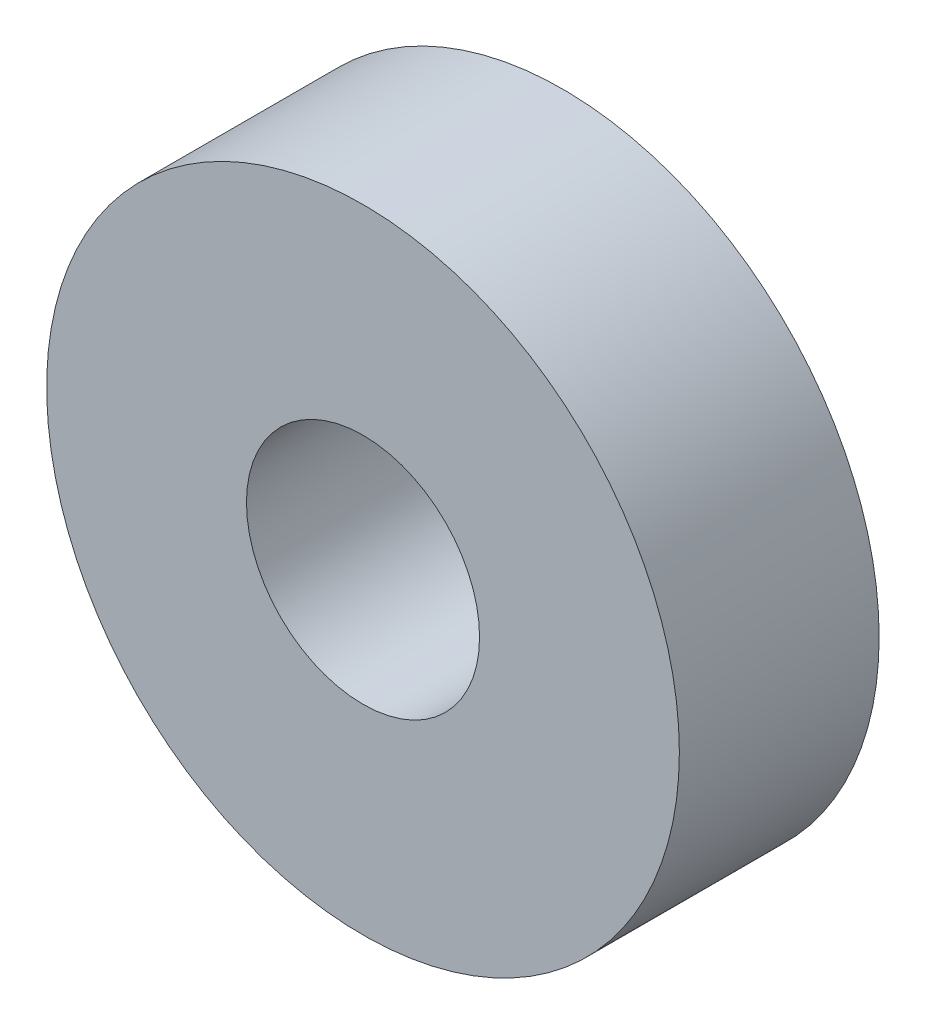
SolidWorks part; units mm, degrees
ref_plane "Plan de face" through (0, 0, 0) normal (0, 0, 1) x (1, 0, 0)
ref_plane "Plan de dessus" through (0, 0, 0) normal (0, 1, 0) x (1, 0, 0)
ref_plane "Plan de droite" through (0, 0, 0) normal (1, 0, 0) x (0, 0, -1)
sketch "Esquisse1" plane through (0, 0, 0) normal (0, 0, 1) x (1, 0, 0)
  circle A0 centre (-30.6971, 0.5894) radius 9.5
  dimension "D1" = 19
extrude "Boss.-Extru.1" add sketch "Esquisse1" along normal blind 6
sketch "Esquisse2" plane through (0, 0, 6) normal (0, 0, 1) x (1, 0, 0)
  circle A0 centre (-30.6971, 0.5894) radius 3.5
  dimension "D1" = 7
extrude "Enlèv. mat.-Extru.1" cut sketch "Esquisse2" against normal up to next
ref_axis "Axe1" through (-30.6971, 0.5894, 0) along (0, 0, 1)
